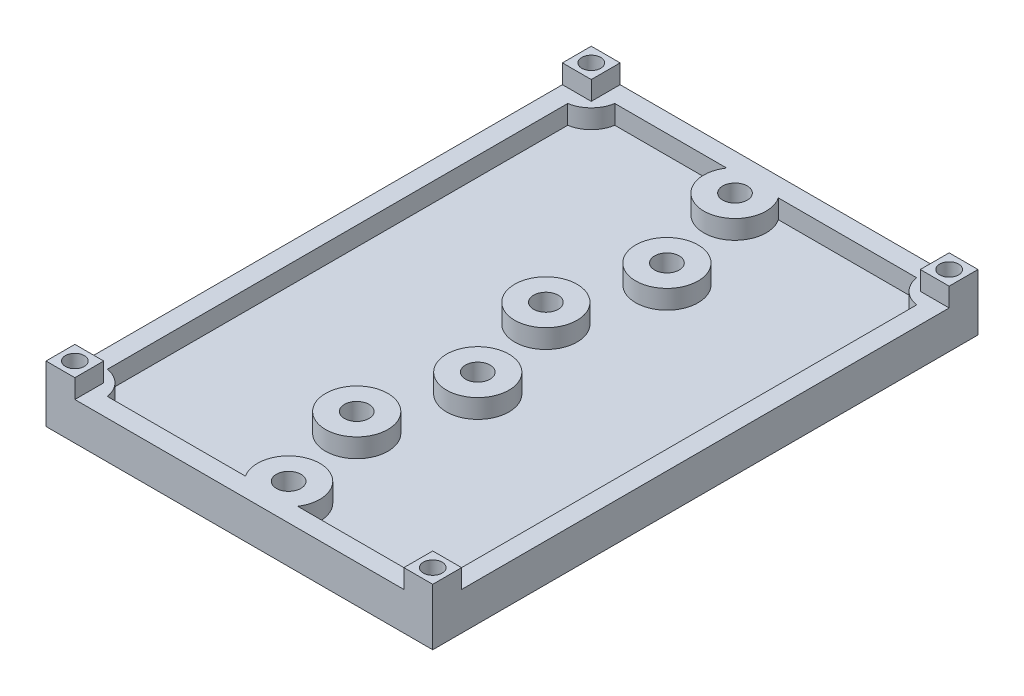
SolidWorks part; units mm, degrees
ref_plane "Front Plane" through (0, 0, 0) normal (0, 0, 1) x (1, 0, 0)
ref_plane "Top Plane" through (0, 0, 0) normal (0, 1, 0) x (1, 0, 0)
ref_plane "Right Plane" through (0, 0, 0) normal (1, 0, 0) x (0, 0, -1)
sketch "Sketch1" plane through (0, 0, 0) normal (0, 1, 0) x (1, 0, 0)
  line L0 (51.1175, 144.145) -> (51.1175, 0) construction
  line L1 (0, 0) -> (102.235, 0)
  line L2 (0, 0) -> (0, 144.145)
  line L3 (0, 144.145) -> (102.235, 144.145)
  line L4 (102.235, 0) -> (102.235, 144.145)
  circle A0 centre (47.6175, 134.525) radius 1.65
  circle A1 centre (54.6175, 109.525) radius 1.65
  circle A2 centre (54.6175, 59.525) radius 1.65
  circle A3 centre (47.6175, 84.525) radius 1.65
  circle A4 centre (54.6175, 9.525) radius 1.65
  circle A5 centre (47.6175, 34.525) radius 1.65
  point P13 (49.0472, 140.205)
  point P20 (54.0633, 114.9532)
  dimension "D5" = 3.3
  dimension "D1" = 102.235
  dimension "D2" = 144.145
  dimension "D3" = 7
  dimension "D4" = 25
  dimension "D6" = 7
  dimension "D7" = 9.62
  dimension "D9" = 50
  dimension "D8" = 3
extrude "Boss-Extrude1" add sketch "Sketch1" along normal blind 10
sketch "Sketch2" plane through (0, 10, 0) normal (0, 1, 0) x (1, 0, 0)
  circle A0 centre (47.6175, 134.525) radius 3.25
  circle A1 centre (54.6175, 109.525) radius 3.25
  circle A2 centre (47.6175, 84.525) radius 3.25
  circle A3 centre (54.6175, 59.525) radius 3.25
  circle A4 centre (47.6175, 34.525) radius 3.25
  circle A5 centre (54.6175, 9.525) radius 3.25
  dimension "D1" = 6.5
extrude "Cut-Extrude1" cut sketch "Sketch2" against normal offset from surface (6 mm away) 4 up to face at (47.6175, 0, -32.875)
sketch "Sketch4" plane through (0, 10, 0) normal (0, 1, 0) x (1, 0, 0)
  line L0 (102.235, 144.145) -> (0, 144.145) construction
  line L1 (0, 144.145) -> (0, 0) construction
  line L2 (0, 72.0725) -> (102.235, 72.0725) construction
  line L3 (102.235, 0) -> (102.235, 144.145) construction
  line L4 (51.1175, 72.0725) -> (51.1175, 144.145) construction
  circle A0 centre (3.815, 140.33) radius 2.5
  circle A4 centre (98.42, 140.33) radius 2.5
  circle A5 centre (98.42, 3.815) radius 2.5
  circle A6 centre (3.815, 3.815) radius 2.5
  dimension "D3" = 5
  dimension "D1" = 3.815
  dimension "D2" = 3.815
extrude "Cut-Extrude2" cut sketch "Sketch4" against normal through all
sketch "Sketch5" plane through (0, 10, 0) normal (0, 1, 0) x (1, 0, 0)
  line L0 (51.1175, 144.145) -> (51.1175, 0) construction
  line L1 (0, 144.145) -> (7.63, 144.145)
  line L2 (0, 144.145) -> (0, 136.515)
  line L3 (0, 136.515) -> (7.63, 136.515)
  line L4 (7.63, 144.145) -> (7.63, 136.515)
  line L5 (102.235, 144.145) -> (0, 144.145) construction
  line L6 (0, 0) -> (102.235, 0) construction
  line L7 (0, 72.0725) -> (102.235, 72.0725) construction
  line L8 (0, 144.145) -> (0, 0) construction
  line L9 (102.235, 0) -> (102.235, 144.145) construction
  line L10 (102.235, 144.145) -> (94.605, 144.145)
  line L11 (102.235, 144.145) -> (102.235, 136.515)
  line L12 (102.235, 136.515) -> (94.605, 136.515)
  line L13 (94.605, 144.145) -> (94.605, 136.515)
  line L14 (102.235, 0) -> (102.235, 7.63)
  line L15 (102.235, 7.63) -> (94.605, 7.63)
  line L16 (94.605, 0) -> (94.605, 7.63)
  line L17 (102.235, 0) -> (94.605, 0)
  line L18 (0, 0) -> (7.63, 0)
  line L19 (0, 0) -> (0, 7.63)
  line L20 (0, 7.63) -> (7.63, 7.63)
  line L21 (7.63, 0) -> (7.63, 7.63)
  circle A0 centre (3.815, 140.33) radius 2.5 construction
  circle A1 centre (3.815, 140.33) radius 2.5
  circle A2 centre (98.42, 140.33) radius 2.5
  circle A3 centre (98.42, 3.815) radius 2.5
  circle A4 centre (3.815, 3.815) radius 2.5
  dimension "D1" = 3.815
extrude "Boss-Extrude2" add sketch "Sketch5" along normal blind 5
shell "Shell4" thickness 5 removed face at (47.6175, 10, -131.275)
